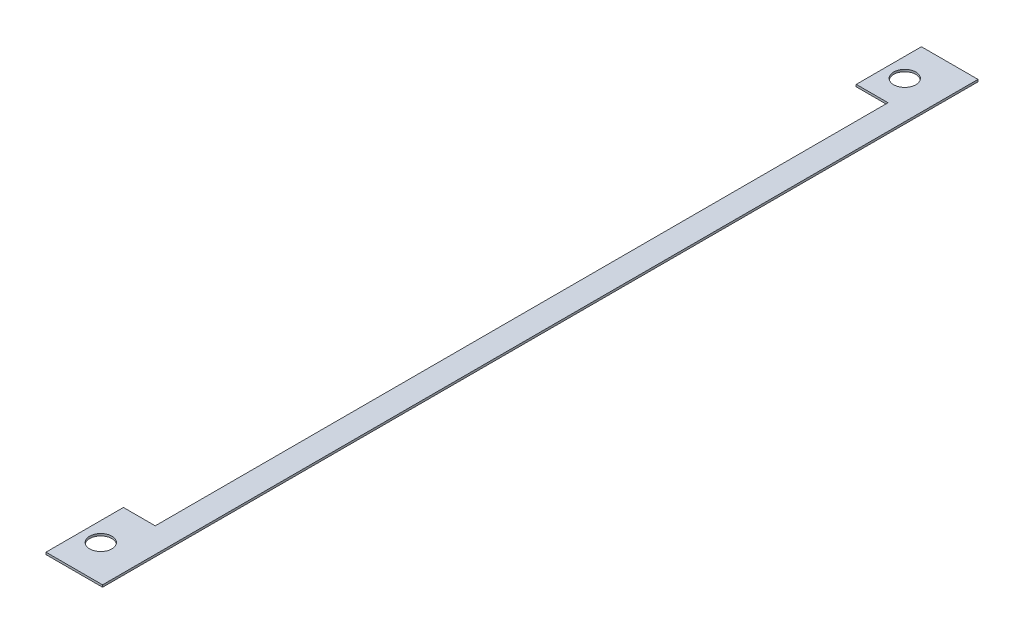
SolidWorks part; units mm, degrees
note: The reader was unsure of these and kept them because the rebuilt part matched: shared geometry of "Sketch2<3>".
ref_plane "Front Plane" through (0, 0, 0) normal (0, 0, 1) x (1, 0, 0)
ref_plane "Top Plane" through (0, 0, 0) normal (0, 1, 0) x (1, 0, 0)
ref_plane "Right Plane" through (0, 0, 0) normal (1, 0, 0) x (0, 0, -1)
sketch "Sketch1" plane through (0, 0, 0) normal (0, 1, 0) x (1, 0, 0)
  line L0 (-6, -6) -> (-6, 106.4)
  line L1 (0, 0) -> (100.4, 0)
  line L2 (0, 0) -> (0, 100.4)
  line L3 (0, 100.4) -> (7.7, 100.4)
  line L4 (100.4, 0) -> (100.4, 40.9)
  line L5 (-6, 106.4) -> (7.7, 106.4)
  line L6 (106.4, -6) -> (106.4, 40.9)
  line L7 (-6, -6) -> (106.4, -6)
  line L8 (100.4, 0) -> (100.4, 100.4) construction
  line L9 (50.2, 100.4) -> (50.2, 0) construction
  line L10 (100.4, 50.2) -> (0, 50.2) construction
  line L11 (92.7, 100.4) -> (92.7, 106.4)
  line L12 (7.7, 100.4) -> (7.7, 106.4)
  line L13 (92.7, 100.4) -> (100.4, 100.4)
  line L14 (0, 100.4) -> (100.4, 100.4) construction
  line L15 (92.7, 106.4) -> (106.4, 106.4)
  line L16 (-6, 106.4) -> (106.4, 106.4) construction
  line L17 (100.4, 59.5) -> (106.4, 59.5)
  line L18 (100.4, 40.9) -> (106.4, 40.9)
  line L19 (100.4, 59.5) -> (100.4, 100.4)
  line L20 (106.4, 59.5) -> (106.4, 106.4)
  line L21 (106.4, -6) -> (106.4, 106.4) construction
  dimension "D1" = 100.4
  dimension "D2" = 100.4
  dimension "D4" = 85
  dimension "D5" = 42.5
  dimension "D6" = 18.6
  dimension "D7" = 9.3
  dimension "D3" = 6
extrude "Boss-Extrude1" add sketch "Sketch1" along normal blind 5.5
sketch "Sketch2" plane through (0, 0, 0) normal (0, -1, 0) x (1, 0, 0)
  line L0 (0, -100.4) -> (7.7, -100.4) construction
  line L1 (-36, 109.6) -> (210, 109.6)
  line L2 (-36, 109.6) -> (-36, -135.4)
  line L3 (-36, -135.4) -> (210, -135.4)
  line L4 (210, 109.6) -> (210, -135.4)
  line L5 (0, 0) -> (0, -100.4) construction
  line L6 (106.4, -106.4) -> (92.7, -106.4) construction
  line L7 (-6, 6) -> (106.4, 6)
  line L8 (-6, 6) -> (-6, -106.4)
  line L9 (-6, -106.4) -> (106.4, -106.4)
  line L10 (106.4, 6) -> (106.4, -106.4)
  dimension "D1" = 246
  dimension "D2" = 245
  dimension "D3" = 210
  dimension "D4" = 210
extrude "Boss-Extrude2" add sketch "Sketch2" along normal blind 9.4 contours L10 L9 L8 L7
extrude "Boss-Extrude3" add sketch "Sketch2<3>" along normal blind 6 from surface at 9.4 contours L2 L3 L4 L1 starting at face at (50.2, -9.4, -50.2)
sketch "Sketch2<3>" plane through (0, 0, 0) normal (0, -1, 0) x (1, 0, 0) same geometry as "Sketch2"
sketch "Sketch3" plane through (0, -9.4, 0) normal (0, 1, 0) x (1, 0, 0)
  line L0 (-36, 135.4) -> (210, 135.4) construction
  line L1 (87, 135.4) -> (87, -109.6) construction
  line L2 (-36, -109.6) -> (210, -109.6) construction
  line L3 (210, 12.9) -> (-36, 12.9) construction
  line L4 (210, -109.6) -> (210, 135.4) construction
  line L5 (-36, -109.6) -> (-36, 135.4) construction
  circle A0 centre (-26.5, 125.4) radius 3.1
  circle A3 centre (-26.5, -99.6) radius 3.1
  circle A4 centre (199.5, 125.4) radius 3.1
  circle A5 centre (199.5, -99.6) radius 3.1
  dimension "D1" = 6.2
  dimension "D5" = 112.5
  dimension "D7" = 112.5
  dimension "D2" = 113.5
  dimension "D3" = 112.5
  dimension "D4" = 112.5
  dimension "D6" = 112.5
extrude "Cut-Extrude1" cut sketch "Sketch3" against normal through all
sketch "Sketch4" plane through (0, -9.4, 0) normal (0, 1, 0) x (1, 0, 0)
  line L0 (-6, -6) -> (106.4, -6) construction
  line L1 (-16, -109.6) -> (49, -109.6)
  line L2 (-36, -89.6) -> (-36, -6)
  line L3 (-36, -6) -> (49, -6)
  line L4 (49, -109.6) -> (49, -6)
  line L5 (-36, -109.6) -> (210, -109.6) construction
  line L8 (-36, -89.6) -> (-22, -89.6)
  line L9 (-16, -109.6) -> (-16, -95.6)
  line L10 (-36, -109.6) -> (-36, 135.4) construction
  arc A0 (-22, -89.6) -> (-16, -95.6) centre (-22, -95.6) cw
  point P15 (-16, -89.6)
  dimension "D4" = 6
  dimension "D1" = 85
  dimension "D2" = 20
  dimension "D3" = 20
extrude "Boss-Extrude4" add sketch "Sketch4" along normal blind 15
sketch "Sketch5" plane through (0, 0, -106.4) normal (0, 0, -1) x (-1, 0, 0)
  line L0 (-107.9, -9.4) -> (-107.9, 13.1)
  line L1 (-8.5, -9.4) -> (7.5, -9.4)
  line L2 (-8.5, -9.4) -> (-8.5, 13.1)
  line L3 (-8.5, 13.1) -> (7.5, 13.1)
  line L4 (7.5, -9.4) -> (7.5, 13.1)
  line L5 (36, -9.4) -> (-210, -9.4) construction
  line L6 (6, 5.5) -> (6, -9.4) construction
  line L7 (-91.9, 13.1) -> (-107.9, 13.1)
  line L8 (-50.2, 0) -> (-50.2, -9.4) construction
  line L9 (-7.7, 0) -> (-92.7, 0) construction
  line L10 (6, -9.4) -> (-106.4, -9.4) construction
  line L11 (-91.9, -9.4) -> (-91.9, 13.1)
  line L12 (-91.9, -9.4) -> (-107.9, -9.4)
  dimension "D1" = 16
  dimension "D2" = 22.5
  dimension "D3" = 14.5
extrude "Boss-Extrude5" add sketch "Sketch5" along normal blind 3.9
sketch "Sketch6" plane through (0, 0, -110.3) normal (0, 0, -1) x (-1, 0, 0)
  line L0 (-8.5, 13.1) -> (-8.5, -9.4) construction
  line L1 (-8.5, 11.1) -> (7.5, 11.1)
  line L2 (-8.5, 11.1) -> (-8.5, -9.4)
  line L3 (-8.5, -9.4) -> (7.5, -9.4)
  line L4 (7.5, 11.1) -> (7.5, -9.4)
  line L5 (7.5, 13.1) -> (-8.5, 13.1) construction
  line L6 (-50.2, 0) -> (-50.2, -9.4) construction
  line L7 (-8.5, 0) -> (-91.9, 0) construction
  line L8 (-8.5, -9.4) -> (-91.9, -9.4) construction
  line L9 (-107.9, 11.1) -> (-107.9, -9.4)
  line L10 (-91.9, -9.4) -> (-107.9, -9.4)
  line L11 (-91.9, 11.1) -> (-91.9, -9.4)
  line L12 (-91.9, 11.1) -> (-107.9, 11.1)
  dimension "D1" = 2
extrude "Cut-Extrude2" cut sketch "Sketch6" against normal blind 3.4
chamfer "Chamfer1" distance 2 angle 45 8 edges at (99.9, 13.1, -106.4) (92.7, 2.75, -106.4) (99.55, 5.5, -106.4) (106.4, -1.95, -106.4) (0.5, 13.1, -106.4) (7.7, 2.75, -106.4) (0.85, 5.5, -106.4) (-6, -1.95, -106.4)
chamfer "Chamfer2" distance 3.05 angle 45 4 edges at (199.5, -9.4, -122.3) (-26.5, -9.4, -122.3) (-26.5, -9.4, 96.5) (199.5, -9.4, 102.7)
chamfer "Chamfer3" distance 3 angle 45 11 edges at (106.4, 5.5, -81.95) (-6, 5.5, -49.2) (6.5, 5.6, 6) (-36, 5.6, 47.8) (-29, 5.6, 89.6) (-16, 5.6, 102.6) (-17.7574, 5.6, 91.3574) (106.4, 5.5, -17.45) (77.7, 5.5, 6) (49, 5.6, 57.8) (16.5, 5.6, 109.6)
chamfer "Chamfer4" distance 3 angle 45 11 edges at (-36, -9.4, -64.7) (129.5, -9.4, 109.6) (-36, -3.4, 89.6) (-36, -3.4, 6) (-34.5, 4.1, 6) (-16, -3.4, 109.6) (49, -3.4, 109.6) (-36, -9.4, 99.6) (87, -9.4, -135.4) (-26, -9.4, 109.6) (210, -9.4, -12.9)
sketch "Sketch8" plane through (0, 5.6, 0) normal (0, 1, 0) x (1, 0, 0)
  line L0 (-33, -6) -> (-33, -86.6) construction
  line L1 (46.1, -6) -> (-33, -6)
  line L2 (46.1, -6) -> (46.1, -11)
  line L3 (46.1, -11) -> (-33, -11)
  line L4 (-33, -6) -> (-33, -11)
  dimension "D1" = 5
extrude "Cut-Extrude3" cut sketch "Sketch8" against normal blind 0.1
chamfer "Chamfer5" distance 3 angle 45 1 edges at (-18, 5.5, 6)
sketch "Sketch9" plane through (0, 0, 109.6) normal (0, 0, 1) x (1, 0, 0)
  line L0 (-36, -15.4) -> (-36, -12.4) construction
  line L1 (-36, -14.8) -> (210, -14.8)
  line L2 (-36, -14.8) -> (-36, 13.1)
  line L3 (-36, 13.1) -> (210, 13.1)
  line L4 (210, -14.8) -> (210, 13.1)
  line L5 (210, -15.4) -> (210, -12.4) construction
  line L6 (91.9, 13.1) -> (107.9, 13.1) construction
  line L7 (-36, -15.4) -> (210, -15.4) construction
  dimension "D1" = 0.6
extrude "Cut-Extrude4" cut sketch "Sketch9" against normal through all
sketch "Sketch10" plane through (0, -14.8, 0) normal (0, 1, 0) x (1, 0, 0)
  line L0 (-13.3203, 126.7447) -> (187.6627, 126.7447)
  line L1 (187.6627, 126.7447) -> (187.6627, 117.1578)
  line L2 (187.6627, 117.1578) -> (203.0702, 117.1578)
  line L3 (203.0702, 117.1578) -> (203.0702, -87.9339)
  line L4 (203.0702, -87.9339) -> (190.4018, -87.9339)
  line L5 (190.4018, -87.9339) -> (190.4018, -102.6566)
  line L6 (190.4018, -102.6566) -> (-18.1137, -102.6566)
  line L7 (-18.1137, -102.6566) -> (-18.1137, -87.9339)
  line L8 (-18.1137, -87.9339) -> (-30.4398, -87.9339)
  line L9 (-30.4398, -87.9339) -> (-30.4398, 117.1578)
  line L10 (-30.4398, 117.1578) -> (-18.1137, 117.1578)
  line L11 (-18.1137, 117.1578) -> (-18.1137, 126.7447)
  line L12 (-18.1137, 126.7447) -> (-13.3203, 126.7447)
extrude "Cut-Extrude5" cut sketch "Sketch10" against normal through all
sketch "Sketch11" plane through (0, -14.8, 0) normal (0, 1, 0) x (1, 0, 0)
  line L5 (-36, -109.6) -> (210, -109.6) construction
  line L6 (-36, 135.4) -> (194.1681, 135.4)
  line L7 (-36, 135.4) -> (-36, -109.6)
  line L8 (-36, -109.6) -> (194.1681, -109.6)
  line L9 (194.1681, 135.4) -> (194.1681, -109.6)
extrude "Cut-Extrude6" cut sketch "Sketch11" against normal through all
